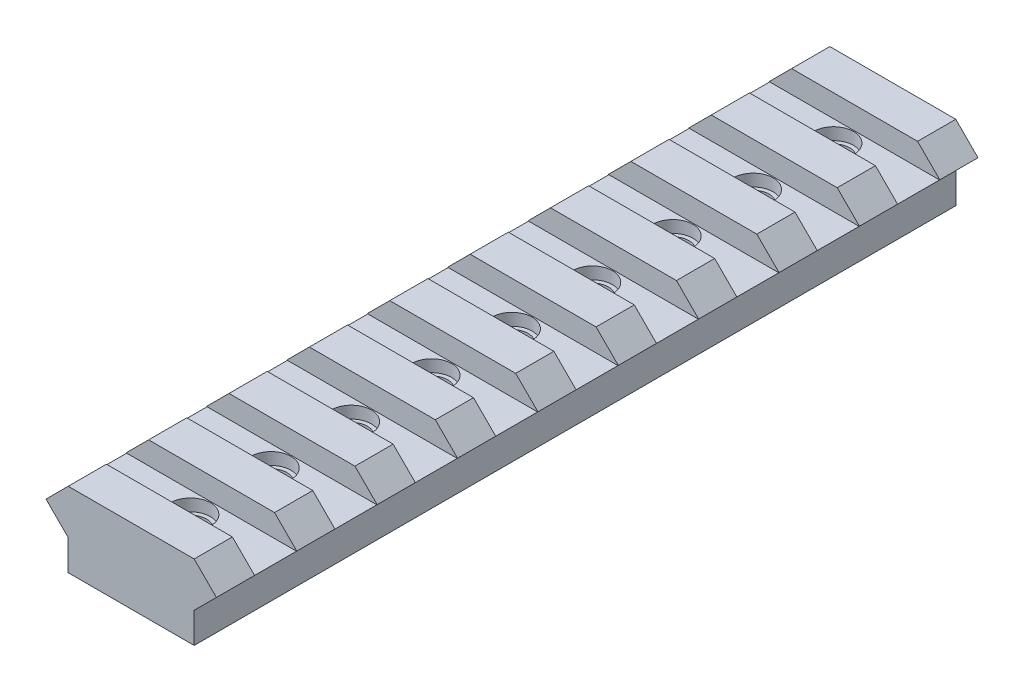
SolidWorks part; units mm, degrees
ref_plane "Płaszczyzna przednia" through (0, 0, 0) normal (0, 0, 1) x (1, 0, 0)
ref_plane "Płaszczyzna górna" through (0, 0, 0) normal (0, 1, 0) x (1, 0, 0)
ref_plane "Płaszczyzna prawa" through (0, 0, 0) normal (1, 0, 0) x (0, 0, -1)
sketch "Szkic1" plane through (0, 0, 0) normal (0, 0, 1) x (1, 0, 0)
  line L0 (-7.835, 4.66) -> (-10.6, 1.895)
  line L5 (-7.835, -4.66) -> (7.835, 4.66) construction
  line L6 (-7.835, 4.66) -> (7.835, -4.66) construction
  line L7 (-10.6, 1.895) -> (-7.835, -0.87)
  line L8 (7.835, 4.66) -> (10.6, 1.895)
  line L9 (10.6, 1.895) -> (7.835, -0.87)
  line L10 (-7.835, -0.87) -> (-7.835, -4.66)
  line L11 (7.835, -4.66) -> (7.835, -0.87)
  line L12 (-7.835, -4.66) -> (7.835, -4.66)
  line L14 (-7.835, 4.66) -> (7.835, 4.66)
  point P0 (0, 0)
  dimension "D1" = 15.67
  dimension "D2" = 9.32
  dimension "D3" = 21.2
  dimension "D4" = 45
extrude "Dodanie-wyciągnięcie2" add sketch "Szkic1" along normal blind 94.75
sketch "Szkic2" plane through (0, 4.66, 0) normal (0, 1, 0) x (1, 0, 0)
  line L1 (-10.6, -14.75) -> (-10.6, -20)
  line L6 (-10.6, -94.75) -> (-10.6, 0) construction
  line L7 (-10.6, -4.75) -> (10.6, -4.75)
  line L8 (-10.6, -4.75) -> (-10.6, -10)
  line L9 (-10.6, -10) -> (10.6, -10)
  line L10 (10.6, -4.75) -> (10.6, -10)
  line L11 (10.6, -94.75) -> (10.6, 0) construction
  line L13 (-10.6, -24.75) -> (-10.6, -30)
  line L15 (-10.6, -34.75) -> (-10.6, -40)
  line L16 (-10.6, -14.75) -> (10.6, -14.75)
  line L18 (-10.6, -20) -> (10.6, -20)
  line L19 (10.6, -14.75) -> (10.6, -20)
  line L20 (-10.6, -24.75) -> (10.6, -24.75)
  line L22 (-10.6, -30) -> (10.6, -30)
  line L23 (10.6, -24.75) -> (10.6, -30)
  line L25 (-10.6, -44.75) -> (-10.6, -50)
  line L27 (-10.6, -54.75) -> (-10.6, -60)
  line L29 (-10.6, -64.75) -> (-10.6, -70)
  line L31 (-10.6, -74.75) -> (-10.6, -80)
  line L33 (-10.6, -84.75) -> (-10.6, -90)
  line L36 (-10.6, -34.75) -> (10.6, -34.75)
  line L38 (-10.6, -40) -> (10.6, -40)
  line L39 (10.6, -34.75) -> (10.6, -40)
  line L40 (-10.6, -44.75) -> (10.6, -44.75)
  line L42 (-10.6, -50) -> (10.6, -50)
  line L43 (10.6, -44.75) -> (10.6, -50)
  line L44 (-10.6, -54.75) -> (10.6, -54.75)
  line L46 (-10.6, -60) -> (10.6, -60)
  line L47 (10.6, -54.75) -> (10.6, -60)
  line L48 (-10.6, -64.75) -> (10.6, -64.75)
  line L50 (-10.6, -70) -> (10.6, -70)
  line L51 (10.6, -64.75) -> (10.6, -70)
  line L52 (-10.6, -74.75) -> (10.6, -74.75)
  line L54 (-10.6, -80) -> (10.6, -80)
  line L55 (10.6, -74.75) -> (10.6, -80)
  line L56 (-10.6, -84.75) -> (10.6, -84.75)
  line L58 (-10.6, -90) -> (10.6, -90)
  line L59 (10.6, -84.75) -> (10.6, -90)
  dimension "D1" = 4.75
  dimension "D2" = 5.25
  dimension "D3" = 4.75
  dimension "D4" = 5.25
  dimension "D5" = 4.75
  dimension "D6" = 5.25
  dimension "D7" = 4.75
  dimension "D8" = 5.25
  dimension "D9" = 4.75
  dimension "D10" = 5.25
  dimension "D11" = 4.75
  dimension "D12" = 5.25
  dimension "D13" = 4.75
  dimension "D14" = 5.25
  dimension "D15" = 4.75
  dimension "D16" = 5.25
  dimension "D17" = 4.75
  dimension "D18" = 5.25
extrude "Wytnij-wyciągnięcie2" cut sketch "Szkic2" against normal blind 2.8
sketch "Szkic3" plane through (0, 1.86, 0) normal (0, 1, 0) x (1, 0, 0)
  circle A0 centre (0, -7.375) radius 2
  circle A1 centre (0, -17.375) radius 2
  circle A2 centre (0, -27.375) radius 2
  circle A3 centre (0, -37.375) radius 2
  circle A4 centre (0, -47.375) radius 2
  circle A5 centre (0, -57.375) radius 2
  circle A6 centre (0, -67.375) radius 2
  circle A7 centre (0, -77.375) radius 2
  circle A8 centre (0, -87.375) radius 2
  dimension "D1" = 7.375
  dimension "D2" = 10
  dimension "D3" = 10
  dimension "D4" = 10
  dimension "D5" = 10
  dimension "D6" = 10
  dimension "D7" = 10
  dimension "D8" = 10
  dimension "D9" = 10
other "Wyrównaj grupę1"
extrude "Wytnij-wyciągnięcie3" cut sketch "Szkic3" against normal blind 6.52
sketch "Szkic4" plane through (0, 1.86, -1.86) normal (0, -1, 0) x (1, 0, 0)
  line L0 (-10.6, 91.86) -> (10.6, 91.86) construction
  circle A0 centre (0, 89.235) radius 2.5
  circle A1 centre (0, 79.235) radius 2.5
  circle A2 centre (0, 69.235) radius 2.5
  circle A3 centre (0, 59.235) radius 2.5
  circle A4 centre (0, 49.235) radius 2.5
  circle A5 centre (0, 39.235) radius 2.5
  circle A6 centre (0, 29.235) radius 2.5
  circle A7 centre (0, 19.235) radius 2.5
  circle A8 centre (0, 9.235) radius 2.5
  point P20 (0, 91.86)
  dimension "D1" = 2.625
  dimension "D2" = 10
  dimension "D3" = 10
  dimension "D4" = 10
  dimension "D5" = 10
  dimension "D6" = 10
  dimension "D7" = 10
  dimension "D8" = 10
  dimension "D9" = 10
extrude "Wytnij-wyciągnięcie4" cut sketch "Szkic4" along normal blind 1.5
